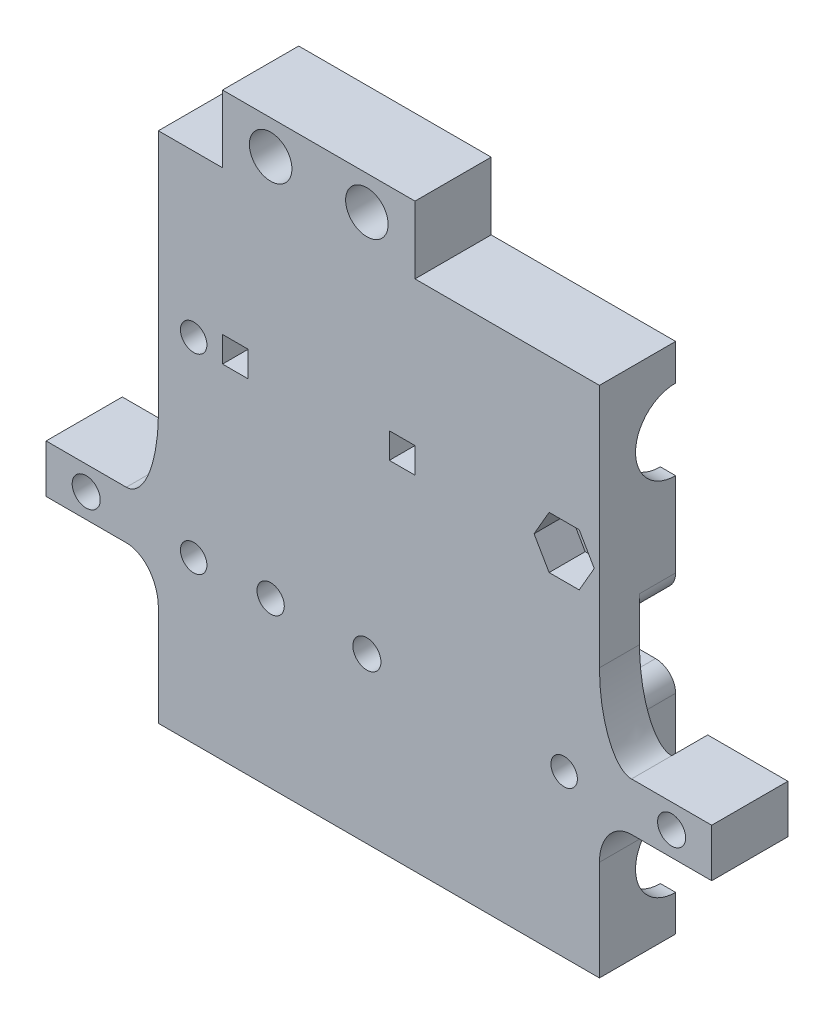
SolidWorks part; units mm, degrees
ref_plane "Płaszczyzna przednia" through (0, 0, 0) normal (0, 0, 1) x (1, 0, 0)
ref_plane "Płaszczyzna górna" through (0, 0, 0) normal (0, 1, 0) x (1, 0, 0)
ref_plane "Płaszczyzna prawa" through (0, 0, 0) normal (1, 0, 0) x (0, 0, -1)
sketch "Szkic1" plane through (0, 0, 0) normal (0, 0, 1) x (1, 0, 0)
  line L0 (21.9203, 0) -> (-21.9203, 0) construction
  line L1 (0, -21.9203) -> (0, 21.9203) construction
  circle A0 centre (21.9203, 0) radius 1.85
  circle A1 centre (-21.9203, 0) radius 1.85
  circle A2 centre (0, 21.9203) radius 1.85
  circle A3 centre (0, 0) radius 11.5
  circle A6 centre (21.9203, 0) radius 3.6 construction
  circle A8 centre (0, 21.9203) radius 3.6 construction
  circle A9 centre (-21.9203, 0) radius 3.6 construction
  point P4 (0, 0)
  point P15 (0, 0)
  dimension "D3" = 3.7
  dimension "D4" = 23
  dimension "D5" = 7.2
  dimension "D1" = 31
sketch "Szkic2" plane through (0, 0, 0) normal (0, 0, 1) x (1, 0, 0)
  line L0 (-0.1428, 34) -> (49999.8572, 34) construction
  line L1 (-0.1428, 30) -> (49999.8572, 30)
  line L2 (-0.1428, 38) -> (49999.8572, 38)
  line L3 (-0.4353, -11) -> (49999.5647, -11) construction
  line L4 (-0.4353, -15) -> (49999.5647, -15)
  line L5 (-0.4353, -7) -> (49999.5647, -7)
  circle A0 centre (0, 0) radius 5
  dimension "D6" = 10
  dimension "D1" = 4
  dimension "D3" = 4
  dimension "D5" = 45
  dimension "D7" = 30
  dimension "D2" = 4
  dimension "D4" = 4
sketch "Szkic8" plane through (0, 0, 0) normal (0, 0, 1) x (1, 0, 0)
  line L0 (0, 0) -> (0, 43.5) construction
  line L1 (-27.5, 43.5) -> (27.5, 43.5)
  line L2 (-27.5, 43.5) -> (-27.5, -20.5)
  line L3 (-27.5, -20.5) -> (27.5, -20.5)
  line L4 (27.5, 43.5) -> (27.5, -20.5)
  line L5 (21.9203, 0) -> (-21.9203, 0) construction
  line L6 (-27.5, -1.5) -> (-2, -1.5)
  line L7 (-2, -1.5) -> (-2, -20.5)
  line L8 (-2, -11) -> (-27.5, -11) construction
  line L9 (-200000.4353, -11) -> (249999.5647, -11) construction
  line L10 (-2, 43.5) -> (-2, 24.5)
  line L11 (-2, 24.5) -> (-27.5, 24.5)
  line L12 (27.5, 34) -> (-27.5, 34) construction
  line L13 (2, 24.5) -> (27.5, 24.5)
  line L14 (-200000.1428, 34) -> (249999.8572, 34) construction
  line L15 (2, -1.5) -> (2, -20.5)
  line L16 (27.5, -1.5) -> (2, -1.5)
  line L17 (2, 43.5) -> (2, 24.5)
  dimension "D1" = 25.5
  dimension "D2" = 19
  dimension "D3" = 4
  dimension "D4" = 9.5
extrude "Dodanie-wyciągnięcie3" add sketch "Szkic8" along normal blind 9.5
sketch "Szkic9" plane through (27.5, 0, 0) normal (1, 0, 0) x (0, 0, -1)
  line L0 (-9.5, 43.5) -> (0, 43.5) construction
  line L3 (0, 43.5) -> (0, -20.5) construction
  circle A0 centre (0, 34) radius 7.6
  dimension "D1" = 15.2
  dimension "D2" = 9.5
extrude "Wytnij-wyciągnięcie2" cut sketch "Szkic9" against normal blind 24.2 from offset 1.9 offset against normal yes
sketch "Szkic10" plane through (27.5, 0, 0) normal (1, 0, 0) x (0, 0, -1)
  line L0 (0, 43.5) -> (0, -20.5) construction
  line L1 (-9.5, -20.5) -> (0, -20.5) construction
  circle A0 centre (0, -11) radius 7.65
  dimension "D1" = 9.5
  dimension "D2" = 15.3
extrude "Wytnij-wyciągnięcie3" cut sketch "Szkic10" against normal blind 24.2 from offset 1.9 offset against normal yes
mirror "Lustro4" about plane through (0, 0, 0) normal (1, 0, 0) of "Wytnij-wyciągnięcie3", "Wytnij-wyciągnięcie2"
sketch "Szkic11" plane through (27.5, 0, 0) normal (1, 0, 0) x (0, 0, -1)
  circle A0 centre (0, 34) radius 5
  circle A1 centre (0, -11) radius 5
  arc A2 (0, -3.35) -> (0, -18.65) centre (0, -11) ccw construction
  arc A3 (0, 41.6) -> (0, 26.4) centre (0, 34) ccw construction
  dimension "D1" = 10
extrude "Wytnij-wyciągnięcie4" cut sketch "Szkic11" against normal through all both and the other way through all
sketch "Szkic42" plane through (0, 0, 0) normal (0, 0, -1) x (-1, 0, 0)
  line L0 (-27.5, 11.5) -> (0, 11.5) construction
  line L1 (-27.5, 29) -> (-27.5, -6) construction
  line L2 (0, 11.5) -> (0, 0) construction
  line L4 (-25.6, -3.35) -> (25.6, -3.35) construction
  line L5 (-25.6, -3.35) -> (-25.6, 26.4) construction
  line L6 (-25.6, 26.4) -> (25.6, 26.4) construction
  line L7 (25.6, -3.35) -> (25.6, 26.4) construction
  line L8 (-23.1, -0.4) -> (23.1, -0.4) construction
  line L9 (-23.1, -0.4) -> (-23.1, 23.4) construction
  line L14 (-23.1, 23.4) -> (23.1, 23.4) construction
  line L15 (23.1, -0.4) -> (23.1, 23.4) construction
  line L16 (0, 23.4) -> (0, -0.4) construction
  line L17 (-23.1, 11.5) -> (23.1, 11.5) construction
  circle A0 centre (23.1, 23.4) radius 1.65
  circle A1 centre (23.1, -0.4) radius 1.65
  circle A2 centre (-23.1, -0.4) radius 1.65
  circle A3 centre (-23.1, 23.4) radius 1.65
  dimension "D1" = 3.3
  dimension "D2" = 2.5
  dimension "D3" = 3
extrude "Wytnij-wyciągnięcie25" cut sketch "Szkic42" against normal up to next
sketch "Szkic43" plane through (0, 0, 9.5) normal (0, 0, 1) x (1, 0, 0)
  line L0 (-27.5, 43.5) -> (27.5, 43.5) construction
  line L1 (-19.5, 43.5) -> (4.5, 43.5)
  line L2 (-19.5, 43.5) -> (-19.5, 51.9)
  line L3 (-19.5, 51.9) -> (4.5, 51.9)
  line L4 (4.5, 43.5) -> (4.5, 51.9)
  line L5 (-27.5, 43.5) -> (-27.5, -20.5) construction
  dimension "D1" = 24
  dimension "D2" = 8
  dimension "D3" = 8.4
extrude "Dodanie-wyciągnięcie4" add sketch "Szkic43" against normal up to surface (9.5 mm away) up to face at (0, 40.6167, 0)
sketch "Szkic44" plane through (0, 0, 9.5) normal (0, 0, 1) x (1, 0, 0)
  line L0 (-19.5, 51.9) -> (-7.5, 51.9) construction
  line L1 (4.5, 51.9) -> (-19.5, 51.9) construction
  line L2 (-7.5, 51.9) -> (4.5, 51.9) construction
  line L3 (-19.5, 47.7) -> (-13.5, 47.7) construction
  line L4 (-19.5, 51.9) -> (-19.5, 43.5) construction
  line L5 (-13.5, 47.7) -> (-13.5, 51.9) construction
  line L6 (-7.5, 51.9) -> (-7.5, 43.441) construction
  circle A0 centre (-13.5, 47.7) radius 2.65
  circle A1 centre (-1.5, 47.7) radius 2.65
  dimension "D1" = 5.3
extrude "Wytnij-wyciągnięcie26" cut sketch "Szkic44" against normal up to next
sketch "Szkic45" plane through (0, 0, 9.5) normal (0, 0, 1) x (1, 0, 0)
  line L0 (4.5, 43.5) -> (27.5, 43.5) construction
  line L1 (-19.5, 25.5) -> (-16.3, 25.5)
  line L2 (-19.5, 25.5) -> (-19.5, 22.3)
  line L3 (-19.5, 22.3) -> (-16.3, 22.3)
  line L4 (-16.3, 25.5) -> (-16.3, 22.3)
  line L5 (1.3, 25.5) -> (4.5, 25.5)
  line L6 (1.3, 25.5) -> (1.3, 22.3)
  line L7 (1.3, 22.3) -> (4.5, 22.3)
  line L8 (4.5, 25.5) -> (4.5, 22.3)
  line L9 (-27.5, 43.5) -> (-27.5, -20.5) construction
  dimension "D1" = 3.2
  dimension "D2" = 18
  dimension "D3" = 8
  dimension "D4" = 24
extrude "Wytnij-wyciągnięcie27" cut sketch "Szkic45" against normal blind 3.4
sketch "Szkic46" plane through (0, 0, 9.5) normal (0, 0, 1) x (1, 0, 0)
  circle A0 centre (-13.5, 0) radius 1.7 construction
  circle A1 centre (-1.5, 0) radius 1.75 construction
  circle A2 centre (-13.5, 0) radius 1.7
  circle A3 centre (-1.5, 0) radius 1.75
extrude "Wytnij-wyciągnięcie28" cut sketch "Szkic46" against normal through all
sketch "Szkic47" plane through (0, 0, 9.5) normal (0, 0, 1) x (1, 0, 0)
  line L1 (21.2236, 20.15) -> (24.9764, 20.15)
  line L2 (24.9764, 20.15) -> (26.8528, 23.4)
  line L3 (26.8528, 23.4) -> (24.9764, 26.65)
  line L4 (24.9764, 26.65) -> (21.2236, 26.65)
  line L5 (21.2236, 26.65) -> (19.3472, 23.4)
  line L6 (19.3472, 23.4) -> (21.2236, 20.15)
  circle A0 centre (23.1, 23.4) radius 3.25 construction
  dimension "D1" = 6.5
extrude "Wytnij-wyciągnięcie29" cut sketch "Szkic47" against normal blind 4.5
sketch "Szkic49" plane through (0, 0, 0) normal (0, 0, -1) x (-1, 0, 0)
  line L0 (27.5, 0) -> (0, 0) construction
  line L1 (27.5, 29) -> (27.5, -6) construction
  line L3 (0, 0) -> (0, 17.1716) construction
  line L4 (31.5, -3) -> (41.5, -3)
  line L5 (31.5, -3) -> (31.5, 3)
  line L6 (31.5, 3) -> (41.5, 3)
  line L7 (41.5, -3) -> (41.5, 3)
  line L8 (36.5, 3) -> (36.5, -3) construction
  line L9 (31.5, 0) -> (41.5, 0) construction
  line L10 (-31.5, 3) -> (-41.5, 3)
  line L11 (-41.5, -3) -> (-41.5, 3)
  line L12 (-31.5, -3) -> (-41.5, -3)
  line L13 (-31.5, -3) -> (-31.5, 3)
  point P4 (36.5, 0)
  dimension "D1" = 6
  dimension "D2" = 4
  dimension "D3" = 10
extrude "Dodanie-wyciągnięcie5" add sketch "Szkic49" against normal blind 4.5 separate body
sketch "Szkic50" plane through (0, 0, 4.5) normal (0, 0, 1) x (1, 0, 0)
  line L0 (-27.5, 43.5) -> (-27.5, -20.5) construction
  line L1 (-41.5, 3) -> (-27.5, 3)
  line L2 (-41.5, 3) -> (-41.5, -3)
  line L3 (-41.5, -3) -> (-27.5, -3)
  line L4 (-27.5, 3) -> (-27.5, -3)
  line L5 (0, 0) -> (0, 22.5677) construction
  line L6 (41.5, -3) -> (27.5, -3)
  line L7 (27.5, 3) -> (27.5, -3)
  line L8 (41.5, 3) -> (27.5, 3)
  line L9 (41.5, 3) -> (41.5, -3)
extrude "Dodanie-wyciągnięcie6" add sketch "Szkic50" along normal up to surface (5 mm away) up to face at (23.1, 23.4, 9.5)
sketch "Szkic51" plane through (0, 0, 0) normal (0, 0, -1) x (-1, 0, 0)
  line L0 (31.5, 3) -> (41.5, -3) construction
  line L1 (0, 0) -> (0, 23.5488) construction
  circle A0 centre (36.5, 0) radius 1.75
  circle A1 centre (-36.5, 0) radius 1.75
  dimension "D1" = 3.5
extrude "Wytnij-wyciągnięcie31" cut sketch "Szkic51" against normal up to next
fillet "Zaokrąglenie2" radius 10 2 edges at (-27.5, 3, 7) (27.5, 3, 7)
fillet "Zaokrąglenie3" radius 5 2 edges at (-27.5, -3, 7) (27.5, -3, 7)
sketch "Szkic52" plane through (0, 0, 0) normal (0, 0, -1) x (-1, 0, 0)
  line L0 (0, 0) -> (41.5, 0) construction
  line L1 (41.5, -3) -> (41.5, 3) construction
  line L2 (-27.5, 29) -> (-27.5, -6) construction
  line L3 (-27.5, 8) -> (27.5, 8)
  line L4 (-27.5, 8) -> (-27.5, 16)
  line L5 (-27.5, 16) -> (27.5, 16)
  line L6 (27.5, 8) -> (27.5, 16)
  line L7 (27.5, 29) -> (27.5, -6) construction
  line L8 (-27.5, 12) -> (27.5, 12) construction
  dimension "D1" = 12
  dimension "D2" = 8
extrude "Wytnij-wyciągnięcie32" cut sketch "Szkic52" against normal blind 4.5
fillet "Zaokrąglenie4" radius 2.5 4 edges at (27.5, 8, 2.25) (27.5, 16, 2.25) (-27.5, 8, 2.25) (-27.5, 16, 2.25)
